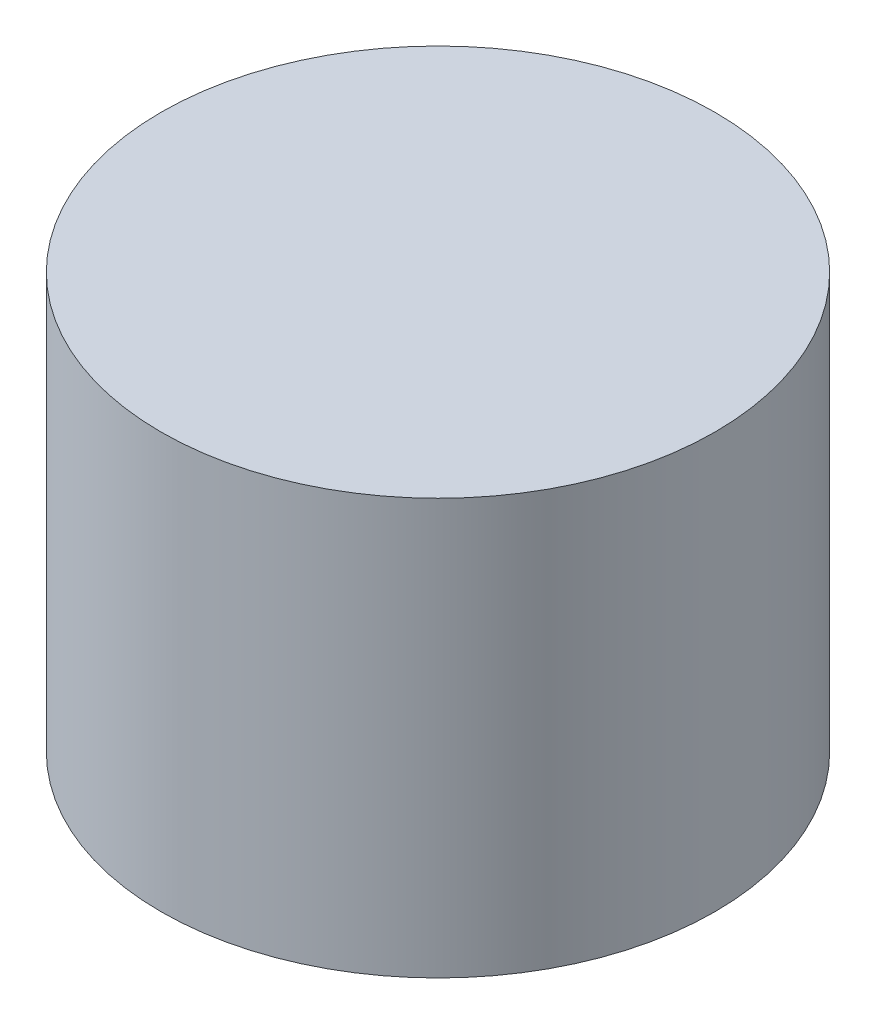
SolidWorks part; units mm, degrees
ref_plane "Front Plane" through (0, 0, 0) normal (0, 0, 1) x (1, 0, 0)
ref_plane "Top Plane" through (0, 0, 0) normal (0, 1, 0) x (1, 0, 0)
ref_plane "Right Plane" through (0, 0, 0) normal (1, 0, 0) x (0, 0, -1)
sketch "Sketch1" plane through (0, 0, 0) normal (0, 1, 0) x (1, 0, 0)
  circle A0 centre (0, 0) radius 2
  dimension "D1" = 4
extrude "Boss-Extrude1" add sketch "Sketch1" along normal blind 3
